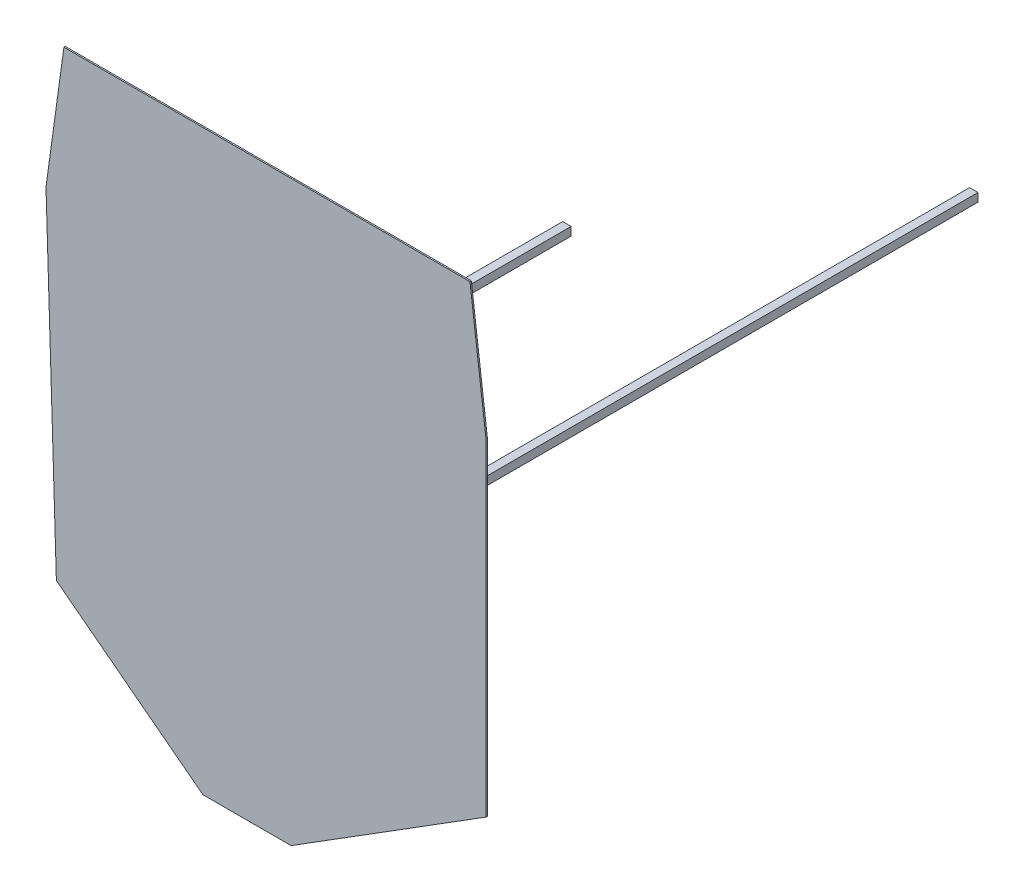
SolidWorks part; units mm, degrees
ref_plane "Front" through (0, 0, 0) normal (0, 0, 1) x (1, 0, 0)
ref_plane "Top" through (0, 0, 0) normal (0, 1, 0) x (1, 0, 0)
ref_plane "Right" through (0, 0, 0) normal (1, 0, 0) x (0, 0, -1)
sketch "Esquisse1" plane through (0, 0, 0) normal (0, 0, 1) x (1, 0, 0)
  line L1 (0, 0) -> (50, 0)
  line L2 (0, 0) -> (0, 50)
  line L3 (0, 50) -> (50, 50)
  line L4 (50, 0) -> (50, 50)
  dimension "D1" = 50
  dimension "D2" = 50
extrude "Boss.-Extru.1" add sketch "Esquisse1" along normal blind 5
sketch "Esquisse2" plane through (0, 0, 5) normal (0, 0, 1) x (1, 0, 0)
  line L0 (-5.6535, 44.5095) -> (1.8863, 52.479)
  line L1 (1.8863, 52.479) -> (274.8364, 52.479)
  line L2 (274.8364, 52.479) -> (286.6056, 43.167)
  line L3 (286.6056, 43.167) -> (287.8096, -119.7901)
  line L4 (287.8096, -119.7901) -> (276.3863, -128.8701)
  line L5 (276.3863, -128.8701) -> (3.8906, -131.1698)
  line L6 (3.8906, -131.1698) -> (-5.6535, -117.6857)
  line L7 (-5.6535, -117.6857) -> (-5.6535, 44.5095)
extrude "Boss.-Extru.2" add sketch "Esquisse2" against normal up to vertex (5 mm away) up to point (0, 50, 0)
sketch "Esquisse3" plane through (0, 0, 0) normal (0, 0, -1) x (-1, 0, 0)
  line L0 (0, -121.7217) -> (6, -121.7217)
  line L1 (6, -121.7217) -> (6, -115.7217)
  line L2 (6, -115.7217) -> (0, -115.7217)
  line L4 (0, -115.7217) -> (0, -121.7217)
  line L6 (-284, 44.2389) -> (-290, 44.2389)
  line L7 (-284, 44.2389) -> (-284, 50.2389)
  line L8 (-284, 50.2389) -> (-290, 50.2389)
  line L9 (-290, 44.2389) -> (-290, 50.2389)
  dimension "D1" = 6
  dimension "D2" = 6
  dimension "D3" = 6
  dimension "D4" = 6
extrude "Boss.-Extru.3" add sketch "Esquisse3" along normal blind 350
sketch "Esquisse4" plane through (0, 0, 5) normal (0, 0, 1) x (1, 0, 0)
  line L0 (-5.5339, 170.1435) -> (283.89, 170.1435)
  line L1 (283.89, 170.1435) -> (295.4804, 77.4204)
  line L2 (295.4804, 77.4204) -> (295.4804, -154.5668)
  line L3 (295.4804, -154.5668) -> (156.3957, -241.7353)
  line L4 (156.3957, -241.7353) -> (93.5299, -241.7353)
  line L5 (93.5299, -241.7353) -> (-10.9091, -161.7784)
  line L6 (-10.9091, -161.7784) -> (-18.3001, 77.4204)
  line L7 (-18.3001, 77.4204) -> (-5.5339, 170.1435)
extrude "Boss.-Extru.4" add sketch "Esquisse4" along normal blind 1
